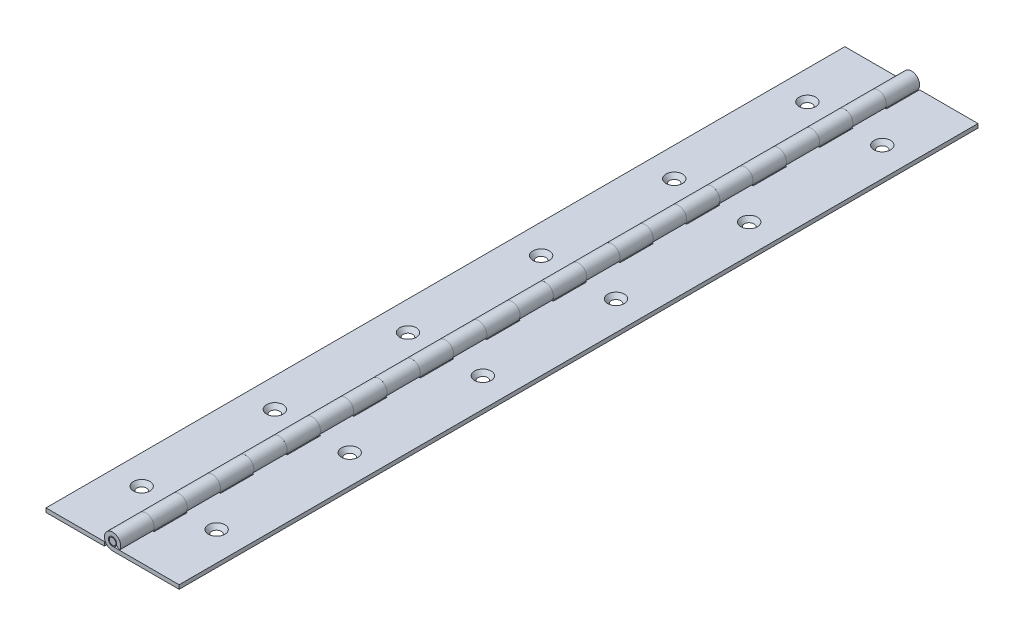
SolidWorks part; units mm, degrees
note: '?' marks a value the reader was unsure of.
material "6061 Alloy"
ref_plane "Front Plane" through (0, 0, 0) normal (0, 0, 1) x (1, 0, 0)
ref_plane "Top Plane" through (0, 0, 0) normal (0, 1, 0) x (1, 0, 0)
ref_plane "Right Plane" through (0, 0, 0) normal (1, 0, 0) x (0, 0, -1)
sketch "Sketch1" plane through (0, 0, 0) normal (0, 0, 1) x (1, 0, 0)
  line L0 (2.6761, -1.5875) -> (25.4, -1.5875)
  line L1 (25.4, -1.5875) -> (25.4, -3.1115)
  line L2 (25.4, -3.1115) -> (0, -3.1115)
  line L3 (0, 0) -> (0, 1.5875) construction
  line L4 (-1.5875, 0) -> (-3.1115, 0) construction
  line L5 (1.4388, -0.6709) -> (2.82, -1.315) construction
  line L6 (-1.4388, -0.6709) -> (-2.82, -1.315) construction
  circle A0 centre (0, 0) radius 1.5875
  circle A1 centre (0, 0) radius 3.1115
  dimension "pin diameter" = 3.175
  dimension "knuckle dia" = 6.223
  dimension "leaf thickness" = 1.524
  dimension "open width" = 50.8
  dimension "D5" = 25
  dimension "D6" = 25
sketch "Sketch2" plane through (0, 0, 0) normal (0, 0, 1) x (1, 0, 0)
  line L0 (25.4, -1.5875) -> (25.4, -3.1115) construction
  line L1 (2.6761, -1.5875) -> (25.4, -1.5875) construction
  line L2 (1.4388, -0.6709) -> (2.82, -1.315) construction
  line L3 (25.4, -3.1115) -> (0, -3.1115) construction
  line L4 (25.4, -1.5875) -> (25.4, -3.1115)
  line L5 (0, -1.5875) -> (25.4, -1.5875)
  line L6 (1.4388, -0.6709) -> (2.82, -1.315)
  line L7 (25.4, -3.1115) -> (0, -3.1115)
  circle A0 centre (0, 0) radius 1.5875 construction
  circle A1 centre (0, 0) radius 3.1115 construction
  arc A2 (1.4388, -0.6709) -> (0, -1.5875) centre (0, 0) ccw
  arc A3 (2.82, -1.315) -> (0, -3.1115) centre (0, 0) ccw
extrude "Extrude1" add sketch "Sketch2" along normal mid plane 304.8
sketch "Sketch3" plane through (0, -1.5875, 0) normal (0, 1, 0) x (1, 0, 0)
  line L1 (-3.1115, 152.4) -> (3.1115, 152.4)
  line L2 (-3.1115, 152.4) -> (-3.1115, 139.7)
  line L3 (-3.1115, 139.7) -> (3.1115, 139.7)
  line L4 (3.1115, 152.4) -> (3.1115, 139.7)
  line L6 (3.1115, 152.4) -> (-3.1115, 152.4) construction
  line L7 (3.1115, -152.4) -> (3.1115, 152.4) construction
  line L8 (-3.1115, 152.4) -> (-3.1115, -152.4) construction
  dimension "knuckle length" = 12.7
extrude "Cut-Extrude1" cut sketch "Sketch3" against normal mid plane 50.8
pattern_linear "LPattern1" count 12 spacing 25.4 along (0, 0, 1) of "Cut-Extrude1"
sketch "Sketch5" plane through (0, 0, -152.4) normal (0, 0, -1) x (-1, 0, 0)
  line L0 (-2.6761, -1.5875) -> (-25.4, -1.5875) construction
  line L1 (-25.4, -3.1115) -> (0, -3.1115) construction
  line L2 (0, -1.5875) -> (25.4, -1.5875)
  line L3 (25.4, -3.1115) -> (0, -3.1115)
  line L4 (1.4388, -0.6709) -> (2.82, -1.315) construction
  line L5 (1.4388, -0.6709) -> (2.82, -1.315)
  line L6 (25.4, -1.5875) -> (25.4, -3.1115)
  line L8 (0, 0) -> (0, -3.1115) construction
  circle A0 centre (0, 0) radius 3.1115 construction
  arc A1 (2.82, -1.315) -> (0, -3.1115) centre (0, 0) ccw
  circle A2 centre (0, 0) radius 1.5875 construction
  arc A3 (1.4388, -0.6709) -> (0, -1.5875) centre (0, 0) ccw
  dimension "D1" = 50.8
extrude "Extrude2" add sketch "Sketch5" against normal blind 12.7 separate body
pattern_linear "LPattern3" count 12 spacing 25.4 along (0, 0, 1) of bodies 104
sketch "Sketch6" plane through (0, 0, -152.4) normal (0, 0, -1) x (-1, 0, 0)
  line L0 (0, -3.1115) -> (25.4, -3.1115) construction
  line L1 (25.4, -1.5875) -> (3.1369, -1.5875)
  line L2 (25.4, -1.5875) -> (25.4, -3.1115)
  line L3 (25.4, -3.1115) -> (3.1369, -3.1115)
  line L4 (3.1369, -1.5875) -> (3.1369, -3.1115)
  line L6 (25.4, -1.5875) -> (0, -1.5875) construction
  line L7 (3.1115, 1.5054) -> (3.1115, -2.5761) construction
  arc A0 (2.82, -1.315) -> (0, -3.1115) centre (0, 0) ccw construction
  dimension "D1" = 0.0254
extrude "Extrude5" add sketch "Sketch6" against normal blind 304.8
sketch "Sketch10" plane through (0, -3.1115, 0) normal (0, 1, 0) x (1, 0, 0)
  line L0 (25.4, -152.4) -> (25.4, 152.4) construction
  line L2 (25.4, 152.4) -> (3.1115, 152.4) construction
  circle A0 centre (14.2875, 127) radius 1.8288
  point P2 (14.2558, 152.4)
  dimension "hole dia" = 3.6576
  dimension "A" = 25.4
  dimension "D" = 11.1125
extrude "Cut-Extrude2" cut sketch "Sketch10" along normal through all draft 41 draft outward yes
pattern_linear "LPattern4" count 6 spacing 50.8 along (0, 0, 1) of "Cut-Extrude2"
mirror "Mirror3" about plane through (0, 0, 0) normal (1, 0, 0) of "LPattern4", "Cut-Extrude2"
sketch "Sketch7" plane through (0, 0, 0) normal (0, 0, 1) x (1, 0, 0)
  circle A0 centre (0, 0) radius 1.5875 construction
  circle A1 centre (0, 0) radius 1.5875
extrude "Extrude4" add sketch "Sketch7" along normal mid plane 304.8 separate body
chamfer "Chamfer1" distance 0.3175 angle 45 2 edges at (1.5875, 0, 152.4) (1.5875, 0, -152.4)
sketch "Sketch8" plane through (0, 0, 0) normal (0, 1, 0) x (1, 0, 0)
  line L0 (25.4, 0) -> (-25.4, 0) construction
  line L1 (25.4, 0) -> (0, 0) construction
  line L2 (-25.4, -152.4) -> (-25.4, 152.4) construction
  line L3 (25.4, -152.4) -> (25.4, 152.4) construction
ref_axis "Axis1" through (-25.4, 0, 0) along (1, 0, 0)?
ref_plane "  " through (0, 0, 0) normal (0, 0.866, 0.5) x (1, 0, 0)
sketch "Sketch9" plane through (0, 0, 0) normal (0, 1, 0) x (1, 0, 0)
  line L0 (3.1115, 139.7) -> (3.1115, 152.4) construction
  point P0 (-25.4, 152.4)
  point P1 (25.4, 152.4)
  point P3 (-25.4, -152.4)
  point P5 (25.4, -152.4)
  point P7 (3.1115, 139.7)
sketch "Sketch11" plane through (0, 0, 0) normal (0, 0, 1) x (1, 0, 0)
  line L0 (-3.1115, 0) -> (-3.1115, -3.1115)
  line L1 (-3.1115, -3.1115) -> (3.1115, -3.1115)
  line L2 (3.1115, -3.1115) -> (3.1115, 0)
  line L3 (0, -3.1115) -> (25.4, -3.1115) construction
  circle A0 centre (0, 0) radius 3.1115
  circle A1 centre (0, 0) radius 3.1115 construction
equation "\"D1@LPattern1\" = \"overall length@Extrude1\"/(\"knuckle length@Sketch3\"*2)"
equation "\"D1@Sketch5\" = \"open width@Sketch1\""
equation "\"D1@LPattern3\" = \"D1@LPattern1\""
equation "\"D1@Extrude4\" = \"overall length@Extrude1\""
equation "\"D3@LPattern1\" = \"knuckle length@Sketch3\"*2"
equation "\"D3@LPattern3\" = \"D3@LPattern1\""
equation "\"D1@Chamfer1\" = \"pin diameter@Sketch1\"*.1"
equation "\"D1@Extrude2\" = \"knuckle length@Sketch3\""
equation "\"D1@Extrude5\" = \"overall length@Extrude1\""
equation "\"D1@LPattern4\" = \"overall length@Extrude1\"/2"
